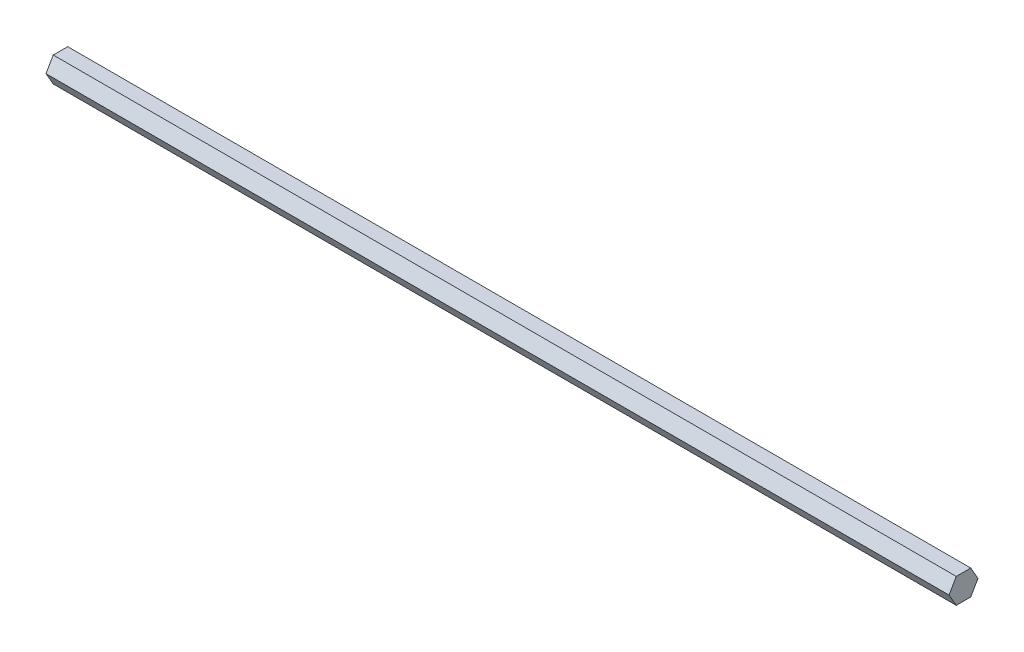
SolidWorks part; units mm, degrees
note: '?' marks a value the reader was unsure of.
material "7075-T6 (SN)"
ref_plane "Front Plane" through (0, 0, 0) normal (0, 0, 1) x (1, 0, 0)
ref_plane "Top Plane" through (0, 0, 0) normal (0, 1, 0) x (1, 0, 0)
ref_plane "Right Plane" through (0, 0, 0) normal (1, 0, 0) x (0, 0, -1)
sketch "Sketch1" plane through (0, 0, 0) normal (1, 0, 0) x (0, 0, -1)
  line L1 (7.3323, 0) -> (3.6662, 6.35)
  line L2 (3.6662, 6.35) -> (-3.6662, 6.35)
  line L3 (-3.6662, 6.35) -> (-7.3323, 0)
  line L4 (-7.3323, 0) -> (-3.6662, -6.35)
  line L5 (-3.6662, -6.35) -> (3.6662, -6.35)
  line L6 (3.6662, -6.35) -> (7.3323, 0)
  circle A0 centre (0, 0) radius 6.35 construction
  dimension "D1" = 12.7
extrude "Boss-Extrude1" add sketch "Sketch1" along normal mid plane 457.2
ref_axis "Axis1" through (-230.505, 0, 0) along (1, 0, 0)?
